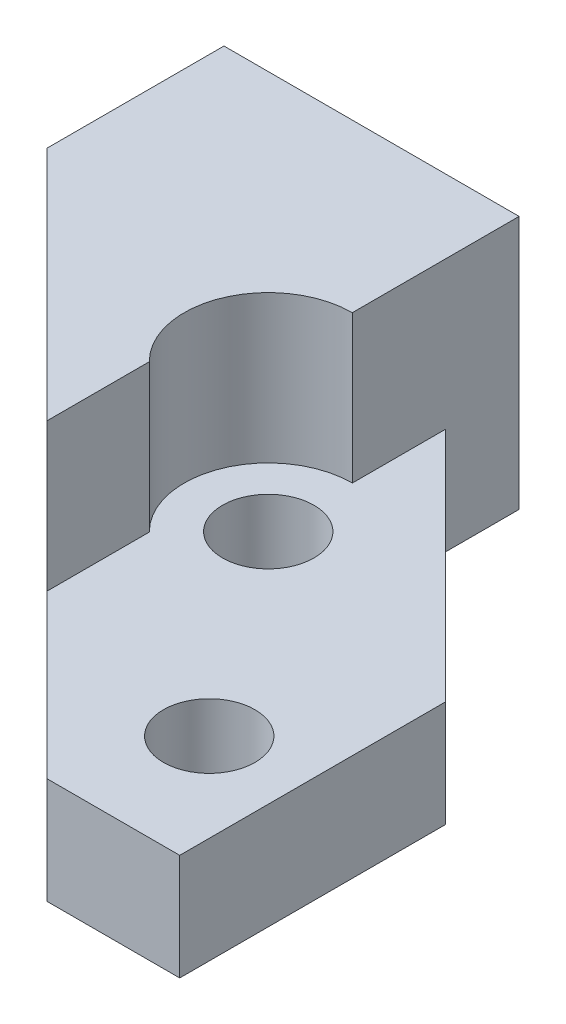
SolidWorks part; units mm, degrees
ref_plane "前视基准面" through (0, 0, 0) normal (0, 0, 1) x (1, 0, 0)
ref_plane "上视基准面" through (0, 0, 0) normal (0, 1, 0) x (1, 0, 0)
ref_plane "右视基准面" through (0, 0, 0) normal (1, 0, 0) x (0, 0, -1)
other "Configuration Table"
sketch "草图1" plane through (0, 0, 0) normal (0, 1, 0) x (1, 0, 0)
  line L1 (0, 0) -> (10, 0)
  line L2 (0, 0) -> (0, 15)
  line L3 (0, 15) -> (10, 15)
  line L4 (10, 0) -> (10, 15)
  circle A0 centre (7, 4) radius 1.55
  circle A1 centre (2, 11) radius 1.55
  dimension "D3" = 7
  dimension "D4" = 5
  dimension "D5" = 3.1
  dimension "D6" = 3.1
  dimension "D8" = 3
  dimension "D1" = 10
  dimension "D2" = 15
  dimension "D7" = 4
extrude "凸台-拉伸1" add sketch "草图1" along normal blind 4
sketch "草图2" plane through (0, 0, 0) normal (-1, 0, 0) x (0, 0, 1)
  line L1 (-5, 9) -> (-19.5, 9)
  line L2 (-5, 9) -> (-5, 0)
  line L3 (-5, 0) -> (-19.5, 0)
  line L4 (-19.5, 9) -> (-19.5, 0)
  line L5 (0, 4) -> (0, 0) construction
  line L6 (-15, 0) -> (0, 0) construction
  dimension "D1" = 5
  dimension "D2" = 14.5
  dimension "D3" = 9
  dimension "D4" = 0
extrude "凸台-拉伸2" add sketch "草图2" along normal blind 6
sketch "草图3" plane through (0, 0, -19.5) normal (0, 0, -1) x (-1, 0, 0)
  line L0 (6, 0) -> (0, 0) construction
  line L2 (0, 4) -> (0, 0) construction
  circle A0 centre (2.9, 3.9) radius 3
  dimension "D1" = 6
  dimension "D2" = 3.9
  dimension "D3" = 2.9
extrude "切除-拉伸1" cut sketch "草图3" against normal blind 3
sketch "草图4" plane through (-6, 0, 0) normal (-1, 0, 0) x (0, 0, 1)
  line L0 (-19.5, 0) -> (-5, 0) construction
  line L1 (-19.5, 9) -> (-11.5, 9)
  line L2 (-19.5, 9) -> (-19.5, 0)
  line L3 (-19.5, 0) -> (-11.5, 0)
  line L4 (-11.5, 9) -> (-11.5, 0)
  dimension "D1" = 8
extrude "凸台-拉伸3" add sketch "草图4" along normal blind 2
sketch "草图5" plane through (0, 0, 0) normal (1, 0, 0) x (0, 0, -1)
  line L0 (0, 0) -> (15, 0) construction
  line L1 (19.5, 9) -> (11.5, 9)
  line L2 (19.5, 9) -> (19.5, 0)
  line L3 (19.5, 0) -> (11.5, 0)
  line L4 (11.5, 9) -> (11.5, 0)
  dimension "D1" = 8
extrude "凸台-拉伸4" add sketch "草图5" along normal blind 2
sketch "草图6" plane through (0, 0, -19.5) normal (0, 0, -1) x (-1, 0, 0)
  circle A0 centre (2.9, 3.9) radius 3.1
  dimension "D1" = 6.2
extrude "切除-拉伸2" cut sketch "草图6" against normal blind 3
sketch "草图7" plane through (0, 4, 0) normal (0, 1, 0) x (1, 0, 0)
  circle A0 centre (2, 11) radius 1.55
  arc A2 (0.5329, 11.5) -> (2, 12.55) centre (2, 11) ccw construction
  dimension "D1" = 0
extrude "切除-拉伸3" cut sketch "草图7" against normal through all
sketch "草图8" plane through (0, 4, 0) normal (0, 1, 0) x (1, 0, 0)
  circle A0 centre (2, 11) radius 2.85
  dimension "D1" = 5.7
extrude "切除-拉伸5" cut sketch "草图8" along normal through all
chamfer "倒角1" distance 2 angle 45 1 edges at (-8, 4.5, -11.5)
chamfer "倒角2" distance 6.5 angle 45 1 edges at (-6, 4.5, -5)
chamfer "倒角3" distance 5.5 angle 45 1 edges at (0, 2, 0)
chamfer "倒角4" distance 6 angle 45 1 edges at (10, 2, -15)
chamfer "倒角5" distance 2 angle 45 1 edges at (2, 2, -15)
chamfer "倒角6" distance 0.4 angle 45 12 edges at (7, 0, -2.45) (-3, 0, -19.5) (-8, 0, -16.5) (-7, 0, -12.5) (-3, 0, -8.5) (2.75, 0, -2.75) (7.75, 0, 0) (10, 0, -4.5) (7, 0, -12) (3, 0, -16) (2, 0, -18.25) (2, 0, -9.45)
